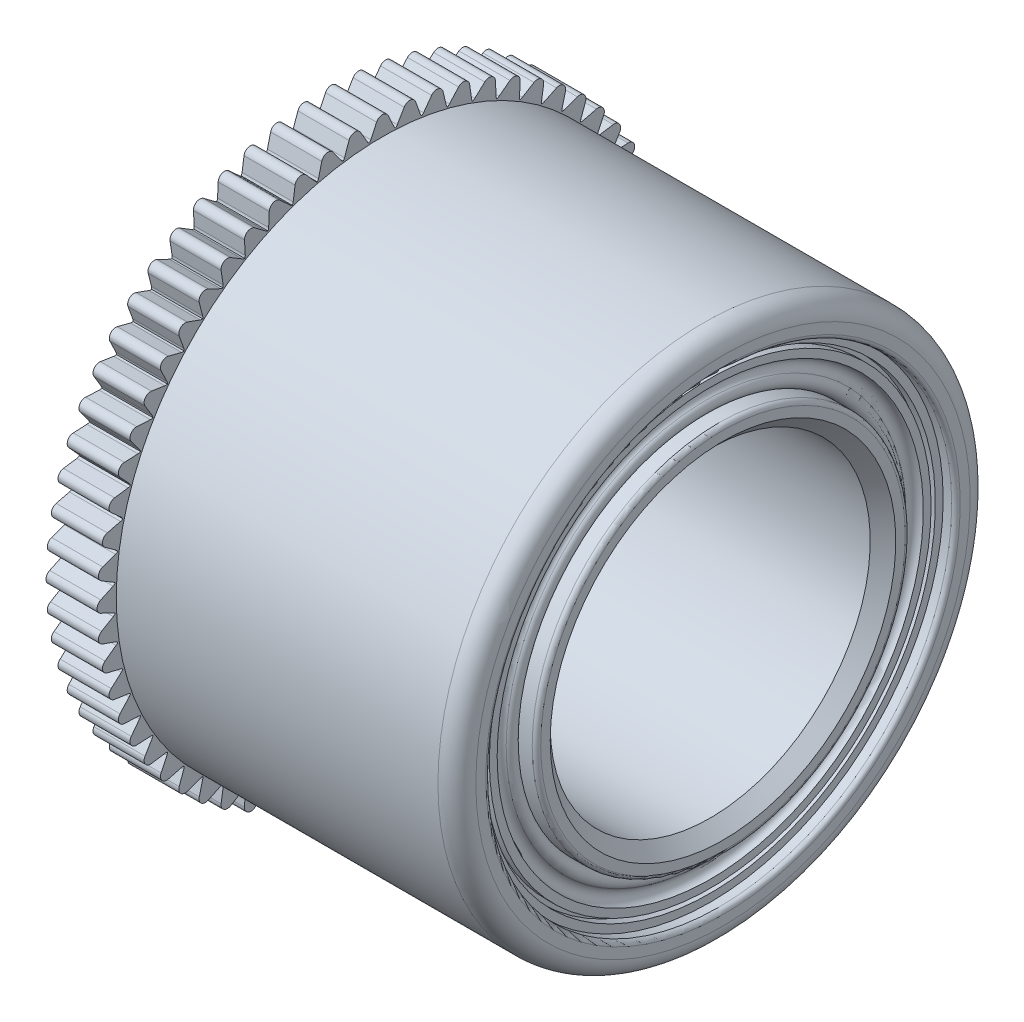
SolidWorks part; units mm, degrees
material "Plain Carbon Steel"
ref_plane "Front Plane" through (0, 0, 0) normal (0, 0, 1) x (1, 0, 0)
ref_plane "Top Plane" through (0, 0, 0) normal (0, 1, 0) x (1, 0, 0)
ref_plane "Right Plane" through (0, 0, 0) normal (1, 0, 0) x (0, 0, -1)
sketch "Sketch1" plane through (0, 0, 0) normal (0, 0, 1) x (1, 0, 0)
  line L0 (-5.842, 0) -> (5.842, 0) construction
  line L1 (-5.842, 4.7727) -> (5.842, 4.7727)
  line L2 (5.842, 4.7727) -> (5.842, 7.9375)
  line L3 (5.842, 7.9375) -> (-4.318, 7.9375)
  line L4 (-4.318, 7.9375) -> (-4.318, 8.509)
  line L5 (-4.318, 8.509) -> (-5.842, 8.509)
  line L6 (-5.842, 8.509) -> (-5.842, 4.7727)
  line L7 (-5.842, -8.509) -> (-4.318, -8.509) construction
  dimension "ID" = 9.5453
  dimension "OD" = 15.875
  dimension "Width" = 11.684
  dimension "Spline OD" = 17.018
  dimension "pt" = 1.524
  dimension "D1" = 3.1648
  dimension "D2" = 17.018
sketch "Sketch2" plane through (0, 0, 0) normal (0, 0, 1) x (1, 0, 0)
  line L0 (5.842, 7.9375) -> (-4.318, 7.9375) construction
  line L1 (5.842, 4.7727) -> (5.842, 5.5639)
  line L2 (5.842, 4.7727) -> (5.842, 7.9375) construction
  line L3 (-5.842, 4.7727) -> (-5.842, 5.5639)
  line L4 (5.842, 7.3723) -> (5.842, 6.9485)
  line L5 (5.842, 6.9485) -> (5.461, 6.9485)
  line L6 (5.461, 6.9485) -> (5.461, 6.7153)
  line L7 (5.461, 6.7153) -> (5.207, 6.7153)
  line L8 (5.207, 6.7153) -> (5.207, 6.5883)
  line L9 (5.207, 6.5883) -> (5.461, 6.5883)
  line L10 (5.461, 6.3551) -> (5.461, 5.5639) construction
  line L11 (5.461, 6.3551) -> (5.207, 6.3551) construction
  line L12 (-5.842, 7.9375) -> (5.2768, 7.9375)
  line L13 (5.842, 5.5639) -> (5.207, 5.5639)
  line L14 (-5.842, 0) -> (5.842, 0) construction
  line L15 (5.461, 6.5883) -> (5.461, 6.3551)
  line L16 (-5.842, 4.7727) -> (5.842, 4.7727)
  line L17 (-5.842, 5.5639) -> (-5.461, 5.5639)
  line L18 (-5.461, 5.5639) -> (-5.461, 6.3551)
  line L19 (-5.461, 6.3551) -> (-5.842, 6.3551)
  line L20 (-5.842, 6.3551) -> (-5.842, 7.9375)
  line L21 (-5.842, 8.509) -> (-5.842, 4.7727) construction
  arc A0 (5.461, 6.3551) -> (5.334, 5.9595) centre (5.461, 6.1369) ccw
  arc A1 (5.2768, 7.9375) -> (5.842, 7.3723) centre (5.2768, 7.3723) cw
  arc A2 (5.334, 5.9595) -> (5.207, 5.5639) centre (5.207, 5.7821) cw
  dimension "D2" = 0.5651
  dimension "D3" = 0.989
  dimension "D5" = 0.127
  dimension "D6" = 0.254
  dimension "D7" = 1.5824
  dimension "D8" = 0.381
  dimension "D9" = 0.381
  dimension "D1" = 0.7912
revolve "Revolve1" add sketch "Sketch2" angle 360 about L14
chamfer "Chamfer1" distance 0.381 angle 45 2 edges at (-5.842, 0, 4.7727) (5.842, 0, 4.7727)
sketch "Sketch4" plane through (-5.842, 0, 0) normal (-1, 0, 0) x (0, 0, 1)
  circle A1 centre (0, 0) radius 6.3551 construction
  circle A2 centre (0, 0) radius 7.4295
  circle A3 centre (0, 0) radius 7.4295
  circle A4 centre (0, 0) radius 6.3551
  dimension "D1" = 0.508
extrude "Cut-Extrude1" cut sketch "Sketch4" against normal blind 0.127
fillet "Fillet1" radius 0.127 4 edges at (5.842, 0, 5.5639) (5.842, 0, 6.9485) (-5.842, 0, 5.5639) (-5.715, 0, 6.3551)
sketch "Sketch3" plane through (-5.842, 0, 0) normal (1, 0, 0) x (0, 0, -1)
  line L0 (0.1727, 8.399) -> (0.3442, 8.031)
  line L1 (-0.1727, 8.399) -> (-0.3442, 8.031)
  line L2 (0, 8.509) -> (0, 4.7727) construction
  line L3 (-0.3924, 7.9278) -> (0, 0) construction
  line L4 (0, 0) -> (0.3924, 7.9278) construction
  line L5 (0, 8.509) -> (0, 7.9375) construction
  line L6 (0, 7.9375) -> (0, 8.509) construction
  line L7 (0, 4.7727) -> (0, 7.9375) construction
  line L8 (0.3924, 7.9278) -> (0.3943, 7.9658)
  line L9 (-0.3924, 7.9278) -> (-0.3943, 7.9658)
  line L10 (0.3924, 7.9278) -> (0.3442, 8.031) construction
  line L11 (-0.3924, 7.9278) -> (-0.3442, 8.031) construction
  arc A0 (-0.1727, 8.399) -> (0.1727, 8.399) centre (0, 8.3185) cw
  circle A2 centre (0, 0) radius 7.9375 construction
  arc A3 (0.3924, 7.9278) -> (-0.3924, 7.9278) centre (0, 0) ccw
  circle A4 centre (0, 0) radius 7.9375 construction
  arc A5 (0.3442, 8.031) -> (0.3943, 7.9658) centre (0.5169, 8.1115) ccw
  arc A6 (-0.3442, 8.031) -> (-0.3943, 7.9658) centre (-0.5169, 8.1115) cw
  dimension "D1" = 0.1905
  dimension "D2" = 50
  dimension "D3" = 5.667
  dimension "D4" = 0.5715
extrude "Boss-Extrude1" add sketch "Sketch3" along normal up to vertex (1.524 mm away) up to point (-4.318, 8.509, 0)
pattern_circular "CirPattern1" count 64 over 360 of "Boss-Extrude1"
sketch "Sketch5" plane through (0, 0, 0) normal (1, 0, 0) x (0, 0, -1)
  circle A0 centre (0, 0) radius 8.509
equation "\"D2@Sketch2\"=\"D3@Sketch2\"/1.750"
equation "\"D3@Sketch2\"=\"D1@Sketch2\" * 1.25"
equation "\"D7@Sketch2\"=\"D1@Sketch1\"/ 2"
equation "\"D1@Sketch2\"=\"D1@Sketch1\"/4"
equation "\"D1@Sketch3\"=\"D4@Sketch3\"/3"
equation "\"D1@CirPattern1\"=(360/\"D3@Sketch3\")"
equation "\"D2@Sketch1\"=\"Spline OD@Sketch1\""
